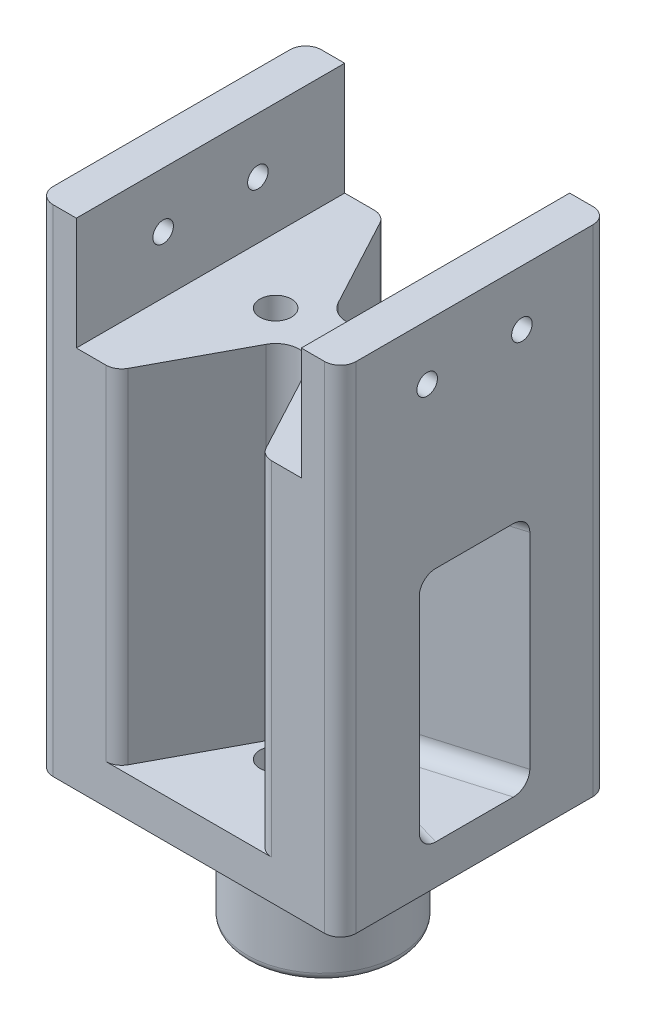
SolidWorks part; units mm, degrees
ref_plane "Front Plane" through (0, 0, 0) normal (0, 0, 1) x (1, 0, 0)
ref_plane "Top Plane" through (0, 0, 0) normal (0, 1, 0) x (1, 0, 0)
ref_plane "Right Plane" through (0, 0, 0) normal (1, 0, 0) x (0, 0, -1)
sketch "Sketch1" plane through (0, 0, 0) normal (0, 1, 0) x (1, 0, 0)
  circle A0 centre (0, 0) radius 9.6
  dimension "D1" = 19.2
extrude "Boss-Extrude1" add sketch "Sketch1" along normal blind 15.7
fillet "Fillet1" radius 1 1 edges at (0, 0, 9.6)
sketch "Sketch3" plane through (0, 15.7, 0) normal (0, 1, 0) x (1, 0, 0)
  line L1 (-14.25, -17) -> (14.25, -17) construction
  line L2 (-14.25, -17) -> (-14.25, 17) construction
  line L3 (-14.25, 17) -> (14.25, 17) construction
  line L4 (14.25, -17) -> (14.25, 17) construction
  line L5 (-14.25, -17) -> (14.25, 17) construction
  line L6 (-14.25, 17) -> (14.25, -17) construction
  line L7 (-19.2, -17) -> (19.2, -17)
  line L8 (-19.2, -17) -> (-19.2, 17)
  line L9 (-19.2, 17) -> (19.2, 17)
  line L10 (19.2, -17) -> (19.2, 17)
  line L11 (-19.2, -17) -> (19.2, 17) construction
  line L12 (-19.2, 17) -> (19.2, -17) construction
  point P1 (0, 0)
  point P7 (0, 0)
  dimension "D1" = 34
  dimension "D2" = 28.5
  dimension "D3" = 0
  dimension "D4" = 4.95
extrude "Boss-Extrude2" add sketch "Sketch3" along normal blind 48.5
sketch "Sketch2" plane through (0, 0, 0) normal (0, -1, 0) x (-1, 0, 0)
  circle A0 centre (0, 0) radius 6 construction
  circle A1 centre (0, -6) radius 1.05
  circle A2 centre (0, 6) radius 1.05
  circle A3 centre (-6, 0) radius 1.05
  circle A4 centre (6, 0) radius 1.05
  dimension "D1" = 12
  dimension "D2" = 2.1
  dimension "D3" = 2.1
  dimension "D4" = 2.1
  dimension "D5" = 2.1
extrude "Cut-Extrude1" cut sketch "Sketch2" against normal through all
sketch "Sketch4" plane through (0, 64.2, 0) normal (0, 1, 0) x (1, 0, 0)
  line L0 (19.2, 17) -> (-19.2, 17) construction
  line L1 (-14.25, -17) -> (14.25, -17)
  line L2 (-14.25, -17) -> (-14.25, 17)
  line L3 (-14.25, 17) -> (14.25, 17)
  line L4 (14.25, -17) -> (14.25, 17)
  line L5 (-14.25, -17) -> (14.25, 17) construction
  line L6 (-14.25, 17) -> (14.25, -17) construction
  line L11 (19.2, -17) -> (19.2, 17)
  line L12 (19.2, 17) -> (-19.2, 17)
  line L13 (-19.2, 17) -> (-19.2, -17)
  line L14 (-19.2, -17) -> (19.2, -17)
  line L15 (19.2, -17) -> (19.2, 17)
  line L16 (19.2, 17) -> (-19.2, 17)
  line L17 (-19.2, 17) -> (-19.2, -17)
  line L18 (-19.2, -17) -> (19.2, -17)
  point P0 (0, 0)
  line M13 (19.2, -17) -> (19.2, 17)
  line M14 (19.2, 17) -> (-19.2, 17)
  line M15 (-19.2, 17) -> (-19.2, -17)
  line M16 (-19.2, -17) -> (19.2, -17)
  dimension "D1" = 28.5
  dimension "D2" = 0
extrude "Boss-Extrude3" add sketch "Sketch4" along normal blind 14.25 contours L2 M16 M14 M15 | L4 M16 M13 M14 region at (-16.725, 64.2, 0) region at (16.725, 64.2, 0)
sketch "Sketch5" plane through (-19.2, 0, 0) normal (-1, 0, 0) x (0, 0, 1)
  line L0 (17, 64.2) -> (-17, 64.2) construction
  line L1 (17, 64.2) -> (-17, 64.2) construction
  line L2 (0, 64.2) -> (0, 78.45) construction
  line L3 (-17, 78.45) -> (17, 78.45) construction
  circle A0 centre (6, 71.45) radius 1.3
  circle A1 centre (-6, 71.45) radius 1.3
  point P4 (0, 64.2)
  dimension "D3" = 2.6
  dimension "D1" = 7.25
  dimension "D2" = 6
extrude "Cut-Extrude2" cut sketch "Sketch5" against normal through all
sketch "Sketch6" plane through (0, 0, 0) normal (0, -1, 0) x (1, 0, 0)
  circle A0 centre (0, 6) radius 2
  circle A1 centre (6, 0) radius 2
  circle A2 centre (0, -6) radius 2
  circle A3 centre (-6, 0) radius 2
  dimension "D1" = 4
  dimension "D2" = 4
  dimension "D3" = 4
  dimension "D4" = 4
extrude "Cut-Extrude3" cut sketch "Sketch6" against normal through all from offset 5 offset against normal yes
sketch "Sketch7" plane through (0, 64.2, 0) normal (0, 1, 0) x (1, 0, 0)
  line L0 (-2.6441, -4.5827) -> (-9.3, -17)
  line L1 (2.6441, -4.5827) -> (9.3, -17)
  line L2 (9.3, -17) -> (-9.3, -17)
  line L3 (-14.25, -17) -> (14.25, -17) construction
  arc A0 (2.6441, -4.5827) -> (-2.6441, -4.5827) centre (0, -6) ccw
  circle A1 centre (0, -6) radius 2 construction
  circle M5 centre (0, -6) radius 2
  line M9 (-14.25, -17) -> (14.25, -17)
  dimension "D1" = 1
  dimension "D2" = 4.95
  dimension "D3" = 4.95
extrude "Cut-Extrude4" cut sketch "Sketch7" against normal offset from surface 5 and the other way through all contours L1 A0 L0 M9 M5 region at (0, 64.2, 12.1347) up to face at (0, 15.7, 9.6)
mirror "Mirror1" about plane through (0, 0, 0) normal (0, 0, 1) of "Cut-Extrude4"
sketch "Sketch8" plane through (0, 64.2, 0) normal (0, 1, 0) x (1, 0, 0)
  line L0 (-5.1553, 2.8786) -> (-19.2, 7)
  line L1 (-19.2, 17) -> (-19.2, -17) construction
  line L2 (-6, 0) -> (-19.2, 0) construction
  line L4 (-19.2, -7) -> (-19.2, 7)
  line L5 (-5.1553, -2.8786) -> (-19.2, -7)
  arc A0 (-5.1553, -2.8786) -> (-5.1553, 2.8786) centre (-6, 0) ccw
  circle A1 centre (-6, 0) radius 2 construction
  dimension "D1" = 1
  dimension "D2" = 7
  dimension "D3" = 7
extrude "Cut-Extrude6" cut sketch "Sketch8" along normal blind 30 from surface starting at face at (0, 20.7, 4)
mirror "Mirror5" about plane through (0, 0, 0) normal (1, 0, 0) of "Cut-Extrude6"
fillet "Fillet3" radius 2 8 edges at (-12.1776, 50.7, 4.9393) (-12.1776, 50.7, -4.9393) (-12.1776, 20.7, 4.9393) (-12.1776, 20.7, -4.9393) (12.1776, 20.7, 4.9393) (12.1776, 50.7, -4.9393) (12.1776, 20.7, -4.9393) (12.1776, 50.7, 4.9393)
fillet "Fillet5" radius 2 4 edges at (19.2, 47.075, -17) (-19.2, 47.075, -17) (-19.2, 47.075, 17) (19.2, 47.075, 17)
fillet "Fillet7" radius 2 4 edges at (-9.3, 42.45, -17) (9.3, 42.45, -17) (9.3, 42.45, 17) (-9.3, 42.45, 17)
